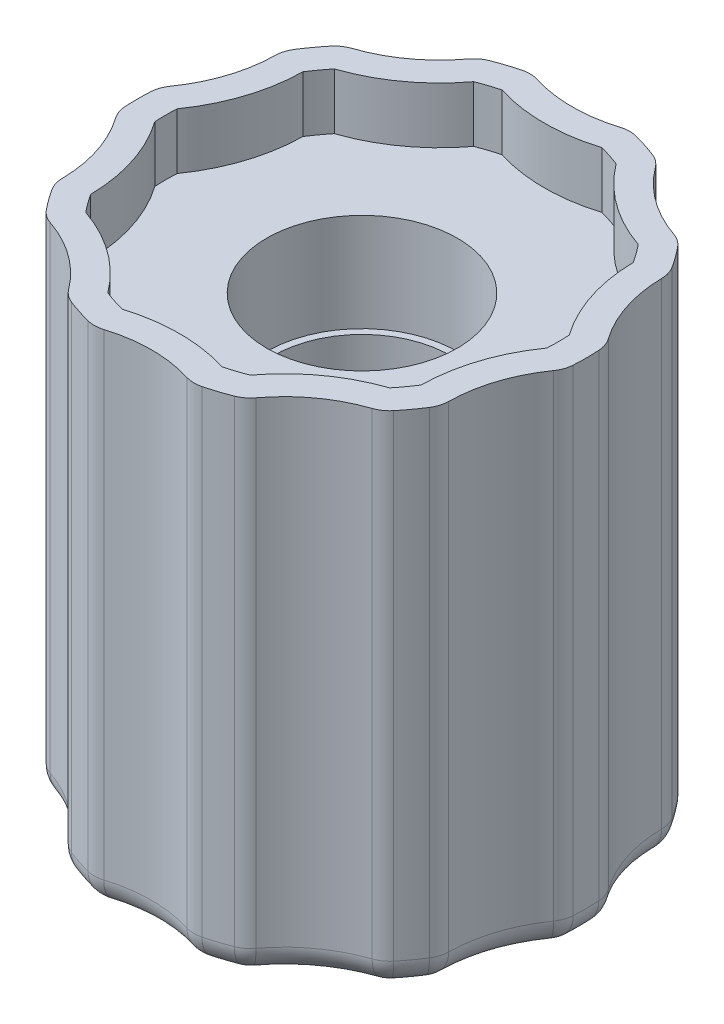
SolidWorks part; units mm, degrees
ref_plane "Plan de face" through (0, 0, 0) normal (0, 0, 1) x (1, 0, 0)
ref_plane "Plan de dessus" through (0, 0, 0) normal (0, 1, 0) x (1, 0, 0)
ref_plane "Plan de droite" through (0, 0, 0) normal (1, 0, 0) x (0, 0, -1)
sketch "Esquisse1" plane through (0, 0, 0) normal (0, 1, 0) x (1, 0, 0)
  circle A0 centre (0, 0) radius 8
  dimension "D1" = 16
extrude "Boss.-Extru.1" add sketch "Esquisse1" along normal blind 16
sketch "Esquisse2" plane through (0, 16, 0) normal (0, 1, 0) x (1, 0, 0)
  line L0 (-2.7423, -1.55) -> (2.7423, -1.55)
  line L1 (0, -1.55) -> (0, 3.15)
  circle A0 centre (0, 0) radius 3.15
  dimension "D1" = 4.7
  dimension "D2" = 6.3
extrude "Enlèv. mat.-Extru.1" cut sketch "Esquisse2" against normal blind 10 contours L0 A0 L1 | L1 A0 L0 region at (-1.4023, 16, -0.5512) region at (1.4023, 16, -0.5512)
sketch "Esquisse3" plane through (0, 16, 0) normal (0, 1, 0) x (1, 0, 0)
  circle A0 centre (0, 12.5) radius 5
  dimension "D1" = 10
  dimension "D2" = 12.5
extrude "Enlèv. mat.-Extru.2" cut sketch "Esquisse3" against normal through all
pattern_circular "Répétition circulaire1" count 10 over 360 about axis through (0, 16, 0) along (0, 1, 0) of "Enlèv. mat.-Extru.2"
fillet "Congé1" radius 1 20 edges at (-1.7332, 8, -7.81) (1.7332, 8, -7.81) (3.1884, 8, -7.3372) (5.9928, 8, -5.2997) (6.8922, 8, -4.0618) (7.9633, 8, -0.7651) (7.9633, 8, 0.7651) (6.8922, 8, 4.0618) (5.9928, 8, 5.2997) (3.1884, 8, 7.3372) (1.7332, 8, 7.81) (-1.7332, 8, 7.81) (-3.1884, 8, 7.3372) (-5.9928, 8, 5.2997) (-6.8922, 8, 4.0618) (-7.9633, 8, 0.7651) (-7.9633, 8, -0.7651) (-6.8922, 8, -4.0618) (-5.9928, 8, -5.2997) (-3.1884, 8, -7.3372)
fillet "Congé2" radius 1 40 edges at (-5.9889, 0, -5.2528) (-6.4721, 0, -4.7023) (-6.8464, 0, -4.0726) (-7.1329, 0, -2.3176) (-7.9326, 0, -0.7294) (-8, 0, 0) (-7.9326, 0, 0.7294) (-7.1329, 0, 2.3176) (-6.8464, 0, 4.0726) (-6.4721, 0, 4.7023) (-5.9889, 0, 5.2528) (-4.4084, 0, 6.0676) (-3.145, 0, 7.319) (-2.4721, 0, 7.6085) (-1.7576, 0, 7.7698) (0, 0, 7.5) (1.7576, 0, 7.7698) (2.4721, 0, 7.6085) (3.145, 0, 7.319) (4.4084, 0, 6.0676) (5.9889, 0, 5.2528) (6.4721, 0, 4.7023) (6.8464, 0, 4.0726) (7.1329, 0, 2.3176) (7.9326, 0, 0.7294) (8, 0, 0) (7.9326, 0, -0.7294) (7.1329, 0, -2.3176) (6.8464, 0, -4.0726) (6.4721, 0, -4.7023) (5.9889, 0, -5.2528) (4.4084, 0, -6.0676) (3.145, 0, -7.319) (2.4721, 0, -7.6085) (1.7576, 0, -7.7698) (0, 0, -7.5) (-1.7576, 0, -7.7698) (-2.4721, 0, -7.6085) (-3.145, 0, -7.319) (-4.4084, 0, -6.0676)
sketch "Esquisse4" plane through (0, 16, 0) normal (0, 1, 0) x (1, 0, 0)
  line L7 (-2.8751, -5.0067) -> (2.8984, -4.9932) construction
  line L8 (2.8984, -4.9932) -> (5.7735, 0.0135) construction
  line L9 (5.7735, 0.0135) -> (2.8751, 5.0067) construction
  line L10 (2.8751, 5.0067) -> (-2.8984, 4.9932) construction
  line L11 (-2.8984, 4.9932) -> (-5.7735, -0.0135) construction
  line L12 (-5.7735, -0.0135) -> (-2.8751, -5.0067) construction
  arc A120 (-6.9886, 0.3995) -> (-5.8887, 3.7846) centre (-11.8882, 3.8627) ccw
  arc A121 (-5.8887, 3.7846) -> (-5.8887, 3.7846) centre (-5.8887, 3.7846) ccw
  arc A122 (-5.4191, 4.431) -> (-5.8887, 3.7846) centre (0, 0) ccw
  arc A123 (-5.4191, 4.431) -> (-5.4191, 4.431) centre (-5.4191, 4.431) ccw
  arc A124 (-5.4191, 4.431) -> (-2.5396, 6.5231) centre (-7.3473, 10.1127) ccw
  arc A125 (-2.5396, 6.5231) -> (-2.5396, 6.5231) centre (-2.5396, 6.5231) ccw
  arc A126 (-1.7796, 6.77) -> (-2.5396, 6.5231) centre (0, 0) ccw
  arc A127 (-1.7796, 6.77) -> (-1.7796, 6.77) centre (-1.7796, 6.77) ccw
  arc A128 (-1.7796, 6.77) -> (1.7796, 6.77) centre (0, 12.5) ccw
  arc A129 (1.7796, 6.77) -> (1.7796, 6.77) centre (1.7796, 6.77) ccw
  arc A130 (2.5396, 6.5231) -> (1.7796, 6.77) centre (0, 0) ccw
  arc A131 (2.5396, 6.5231) -> (2.5396, 6.5231) centre (2.5396, 6.5231) ccw
  arc A132 (2.5396, 6.5231) -> (5.4191, 4.431) centre (7.3473, 10.1127) ccw
  arc A133 (5.4191, 4.431) -> (5.4191, 4.431) centre (5.4191, 4.431) ccw
  arc A134 (5.8887, 3.7846) -> (5.4191, 4.431) centre (0, 0) ccw
  arc A135 (5.8887, 3.7846) -> (5.8887, 3.7846) centre (5.8887, 3.7846) ccw
  arc A136 (5.8887, 3.7846) -> (6.9886, 0.3995) centre (11.8882, 3.8627) ccw
  arc A137 (6.9886, 0.3995) -> (6.9886, 0.3995) centre (6.9886, 0.3995) ccw
  arc A138 (6.9886, -0.3995) -> (6.9886, 0.3995) centre (0, 0) ccw
  arc A139 (6.9886, -0.3995) -> (6.9886, -0.3995) centre (6.9886, -0.3995) ccw
  arc A140 (6.9886, -0.3995) -> (5.8887, -3.7846) centre (11.8882, -3.8627) ccw
  arc A141 (5.8887, -3.7846) -> (5.8887, -3.7846) centre (5.8887, -3.7846) ccw
  arc A142 (5.4191, -4.431) -> (5.8887, -3.7846) centre (0, 0) ccw
  arc A143 (5.4191, -4.431) -> (5.4191, -4.431) centre (5.4191, -4.431) ccw
  arc A144 (5.4191, -4.431) -> (2.5396, -6.5231) centre (7.3473, -10.1127) ccw
  arc A145 (2.5396, -6.5231) -> (2.5396, -6.5231) centre (2.5396, -6.5231) ccw
  arc A146 (1.7796, -6.77) -> (2.5396, -6.5231) centre (0, 0) ccw
  arc A147 (1.7796, -6.77) -> (1.7796, -6.77) centre (1.7796, -6.77) ccw
  arc A148 (1.7796, -6.77) -> (-1.7796, -6.77) centre (0, -12.5) ccw
  arc A149 (-1.7796, -6.77) -> (-1.7796, -6.77) centre (-1.7796, -6.77) ccw
  arc A150 (-2.5396, -6.5231) -> (-1.7796, -6.77) centre (0, 0) ccw
  arc A151 (-2.5396, -6.5231) -> (-2.5396, -6.5231) centre (-2.5396, -6.5231) ccw
  arc A152 (-2.5396, -6.5231) -> (-5.4191, -4.431) centre (-7.3473, -10.1127) ccw
  arc A153 (-5.4191, -4.431) -> (-5.4191, -4.431) centre (-5.4191, -4.431) ccw
  arc A154 (-5.8887, -3.7846) -> (-5.4191, -4.431) centre (0, 0) ccw
  arc A155 (-5.8887, -3.7846) -> (-5.8887, -3.7846) centre (-5.8887, -3.7846) ccw
  arc A156 (-5.8887, -3.7846) -> (-6.9886, -0.3995) centre (-11.8882, -3.8627) ccw
  arc A157 (-6.9886, -0.3995) -> (-6.9886, -0.3995) centre (-6.9886, -0.3995) ccw
  arc A158 (-6.9886, 0.3995) -> (-6.9886, -0.3995) centre (0, 0) ccw
  arc A159 (-6.9886, 0.3995) -> (-6.9886, 0.3995) centre (-6.9886, 0.3995) ccw
  arc A160 (-1.483, 7.725) -> (1.483, 7.725) centre (0, 12.5) ccw
  arc A161 (-1.483, 7.725) -> (-2.0339, 7.7371) centre (-1.7796, 6.77) ccw
  arc A162 (-2.0339, 7.7371) -> (-2.9023, 7.455) centre (0, 0) ccw
  arc A163 (-2.9023, 7.455) -> (-3.3408, 7.1214) centre (-2.5396, 6.5231) ccw
  arc A164 (-5.7404, 5.378) -> (-3.3408, 7.1214) centre (-7.3473, 10.1127) ccw
  arc A165 (-5.7404, 5.378) -> (-6.1932, 5.064) centre (-5.4191, 4.431) ccw
  arc A166 (-6.1932, 5.064) -> (-6.73, 4.3252) centre (0, 0) ccw
  arc A167 (-6.73, 4.3252) -> (-6.8886, 3.7976) centre (-5.8887, 3.7846) ccw
  arc A168 (-7.8052, 0.9767) -> (-6.8886, 3.7976) centre (-11.8882, 3.8627) ccw
  arc A169 (-7.8052, 0.9767) -> (-7.987, 0.4566) centre (-6.9886, 0.3995) ccw
  arc A170 (-7.987, 0.4566) -> (-7.987, -0.4566) centre (0, 0) ccw
  arc A171 (-7.987, -0.4566) -> (-7.8052, -0.9767) centre (-6.9886, -0.3995) ccw
  arc A172 (-6.8886, -3.7976) -> (-7.8052, -0.9767) centre (-11.8882, -3.8627) ccw
  arc A173 (-6.8886, -3.7976) -> (-6.73, -4.3252) centre (-5.8887, -3.7846) ccw
  arc A174 (-6.73, -4.3252) -> (-6.1932, -5.064) centre (0, 0) ccw
  arc A175 (-6.1932, -5.064) -> (-5.7404, -5.378) centre (-5.4191, -4.431) ccw
  arc A176 (-3.3408, -7.1214) -> (-5.7404, -5.378) centre (-7.3473, -10.1127) ccw
  arc A177 (-3.3408, -7.1214) -> (-2.9023, -7.455) centre (-2.5396, -6.5231) ccw
  arc A178 (-2.9023, -7.455) -> (-2.0339, -7.7371) centre (0, 0) ccw
  arc A179 (-2.0339, -7.7371) -> (-1.483, -7.725) centre (-1.7796, -6.77) ccw
  arc A180 (1.483, -7.725) -> (-1.483, -7.725) centre (0, -12.5) ccw
  arc A181 (1.483, -7.725) -> (2.0339, -7.7371) centre (1.7796, -6.77) ccw
  arc A182 (2.0339, -7.7371) -> (2.9023, -7.455) centre (0, 0) ccw
  arc A183 (2.9023, -7.455) -> (3.3408, -7.1214) centre (2.5396, -6.5231) ccw
  arc A184 (5.7404, -5.378) -> (3.3408, -7.1214) centre (7.3473, -10.1127) ccw
  arc A185 (5.7404, -5.378) -> (6.1932, -5.064) centre (5.4191, -4.431) ccw
  arc A186 (6.1932, -5.064) -> (6.73, -4.3252) centre (0, 0) ccw
  arc A187 (6.73, -4.3252) -> (6.8886, -3.7976) centre (5.8887, -3.7846) ccw
  arc A188 (7.8052, -0.9767) -> (6.8886, -3.7976) centre (11.8882, -3.8627) ccw
  arc A189 (7.8052, -0.9767) -> (7.987, -0.4566) centre (6.9886, -0.3995) ccw
  arc A190 (7.987, -0.4566) -> (7.987, 0.4566) centre (0, 0) ccw
  arc A191 (7.987, 0.4566) -> (7.8052, 0.9767) centre (6.9886, 0.3995) ccw
  arc A192 (6.8886, 3.7976) -> (7.8052, 0.9767) centre (11.8882, 3.8627) ccw
  arc A193 (6.8886, 3.7976) -> (6.73, 4.3252) centre (5.8887, 3.7846) ccw
  arc A194 (6.73, 4.3252) -> (6.1932, 5.064) centre (0, 0) ccw
  arc A195 (6.1932, 5.064) -> (5.7404, 5.378) centre (5.4191, 4.431) ccw
  arc A196 (3.3408, 7.1214) -> (5.7404, 5.378) centre (7.3473, 10.1127) ccw
  arc A197 (3.3408, 7.1214) -> (2.9023, 7.455) centre (2.5396, 6.5231) ccw
  arc A198 (2.9023, 7.455) -> (2.0339, 7.7371) centre (0, 0) ccw
  arc A199 (2.0339, 7.7371) -> (1.483, 7.725) centre (1.7796, 6.77) ccw
  arc A200 (-1.483, 7.725) -> (1.483, 7.725) centre (0, 12.5) ccw
  arc A201 (-1.483, 7.725) -> (-2.0339, 7.7371) centre (-1.7796, 6.77) ccw
  arc A202 (-2.0339, 7.7371) -> (-2.9023, 7.455) centre (0, 0) ccw
  arc A203 (-2.9023, 7.455) -> (-3.3408, 7.1214) centre (-2.5396, 6.5231) ccw
  arc A204 (-5.7404, 5.378) -> (-3.3408, 7.1214) centre (-7.3473, 10.1127) ccw
  arc A205 (-5.7404, 5.378) -> (-6.1932, 5.064) centre (-5.4191, 4.431) ccw
  arc A206 (-6.1932, 5.064) -> (-6.73, 4.3252) centre (0, 0) ccw
  arc A207 (-6.73, 4.3252) -> (-6.8886, 3.7976) centre (-5.8887, 3.7846) ccw
  arc A208 (-7.8052, 0.9767) -> (-6.8886, 3.7976) centre (-11.8882, 3.8627) ccw
  arc A209 (-7.8052, 0.9767) -> (-7.987, 0.4566) centre (-6.9886, 0.3995) ccw
  arc A210 (-7.987, 0.4566) -> (-7.987, -0.4566) centre (0, 0) ccw
  arc A211 (-7.987, -0.4566) -> (-7.8052, -0.9767) centre (-6.9886, -0.3995) ccw
  arc A212 (-6.8886, -3.7976) -> (-7.8052, -0.9767) centre (-11.8882, -3.8627) ccw
  arc A213 (-6.8886, -3.7976) -> (-6.73, -4.3252) centre (-5.8887, -3.7846) ccw
  arc A214 (-6.73, -4.3252) -> (-6.1932, -5.064) centre (0, 0) ccw
  arc A215 (-6.1932, -5.064) -> (-5.7404, -5.378) centre (-5.4191, -4.431) ccw
  arc A216 (-3.3408, -7.1214) -> (-5.7404, -5.378) centre (-7.3473, -10.1127) ccw
  arc A217 (-3.3408, -7.1214) -> (-2.9023, -7.455) centre (-2.5396, -6.5231) ccw
  arc A218 (-2.9023, -7.455) -> (-2.0339, -7.7371) centre (0, 0) ccw
  arc A219 (-2.0339, -7.7371) -> (-1.483, -7.725) centre (-1.7796, -6.77) ccw
  arc A220 (1.483, -7.725) -> (-1.483, -7.725) centre (0, -12.5) ccw
  arc A221 (1.483, -7.725) -> (2.0339, -7.7371) centre (1.7796, -6.77) ccw
  arc A222 (2.0339, -7.7371) -> (2.9023, -7.455) centre (0, 0) ccw
  arc A223 (2.9023, -7.455) -> (3.3408, -7.1214) centre (2.5396, -6.5231) ccw
  arc A224 (5.7404, -5.378) -> (3.3408, -7.1214) centre (7.3473, -10.1127) ccw
  arc A225 (5.7404, -5.378) -> (6.1932, -5.064) centre (5.4191, -4.431) ccw
  arc A226 (6.1932, -5.064) -> (6.73, -4.3252) centre (0, 0) ccw
  arc A227 (6.73, -4.3252) -> (6.8886, -3.7976) centre (5.8887, -3.7846) ccw
  arc A228 (7.8052, -0.9767) -> (6.8886, -3.7976) centre (11.8882, -3.8627) ccw
  arc A229 (7.8052, -0.9767) -> (7.987, -0.4566) centre (6.9886, -0.3995) ccw
  arc A230 (7.987, -0.4566) -> (7.987, 0.4566) centre (0, 0) ccw
  arc A231 (7.987, 0.4566) -> (7.8052, 0.9767) centre (6.9886, 0.3995) ccw
  arc A232 (6.8886, 3.7976) -> (7.8052, 0.9767) centre (11.8882, 3.8627) ccw
  arc A233 (6.8886, 3.7976) -> (6.73, 4.3252) centre (5.8887, 3.7846) ccw
  arc A234 (6.73, 4.3252) -> (6.1932, 5.064) centre (0, 0) ccw
  arc A235 (6.1932, 5.064) -> (5.7404, 5.378) centre (5.4191, 4.431) ccw
  arc A236 (3.3408, 7.1214) -> (5.7404, 5.378) centre (7.3473, 10.1127) ccw
  arc A237 (3.3408, 7.1214) -> (2.9023, 7.455) centre (2.5396, 6.5231) ccw
  arc A238 (2.9023, 7.455) -> (2.0339, 7.7371) centre (0, 0) ccw
  arc A239 (2.0339, 7.7371) -> (1.483, 7.725) centre (1.7796, 6.77) ccw
  circle A240 centre (0, 0) radius 5 construction
  dimension "D2" = 1
  dimension "D3" = 10
  dimension "D1" = 0
extrude "Boss.-Extru.2" add sketch "Esquisse4" along normal blind 2
sketch "Esquisse5" plane through (0, 16, 0) normal (0, 1, 0) x (1, 0, 0)
  circle A0 centre (0, 0) radius 3.4
  dimension "D1" = 6.8
extrude "Enlèv. mat.-Extru.3" cut sketch "Esquisse5" against normal blind 3.5
sketch "Esquisse6" plane through (0, 12.5, 0) normal (0, 1, 0) x (1, 0, 0)
  line L0 (-2.7423, -1.55) -> (2.7423, -1.55) construction
  circle A0 centre (0, -1.55) radius 0.5
  dimension "D1" = 1
extrude "Enlèv. mat.-Extru.4" cut sketch "Esquisse6" against normal up to surface (6.5 mm away) up to face at (0, 6, -0.8)
fillet "Congé3" radius 2 2 edges at (0.5, 9.25, 1.55) (-0.5, 9.25, 1.55)
